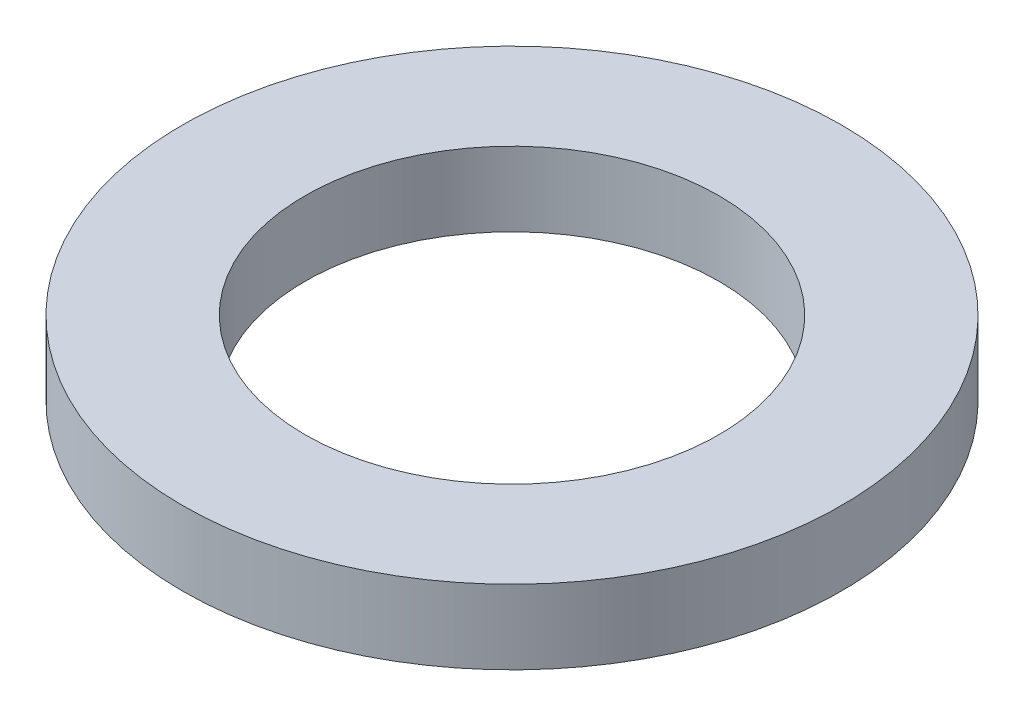
SolidWorks part; units mm, degrees
material "PTFE (general)"
ref_plane "Front Plane" through (0, 0, 0) normal (0, 0, 1) x (1, 0, 0)
ref_plane "Top Plane" through (0, 0, 0) normal (0, 1, 0) x (1, 0, 0)
ref_plane "Right Plane" through (0, 0, 0) normal (1, 0, 0) x (0, 0, -1)
sketch "Sketch1" plane through (0, 0, 0) normal (0, 0, 1) x (1, 0, 0)
  line L0 (0, 0) -> (0, -5.3675) construction
  line L1 (5.025, 0) -> (8, 0)
  line L2 (8, 0) -> (8, -1.8)
  line L3 (8, -1.8) -> (5.9, -1.8)
  line L4 (5.9, -1.8) -> (5.9, -2)
  line L5 (5.9, -2) -> (5.5, -2)
  line L6 (5.5, -2) -> (5.5, -1.8)
  line L7 (5.5, -1.8) -> (5.025, -1.8)
  line L8 (5.025, -1.8) -> (5.025, 0)
  dimension "D1" = 10.05
  dimension "D2" = 1.8
  dimension "D3" = 0.2
  dimension "D4" = 16
  dimension "D5" = 0.4
  dimension "D6" = 11
revolve "Revolve1" add sketch "Sketch1" angle 360 about L0
